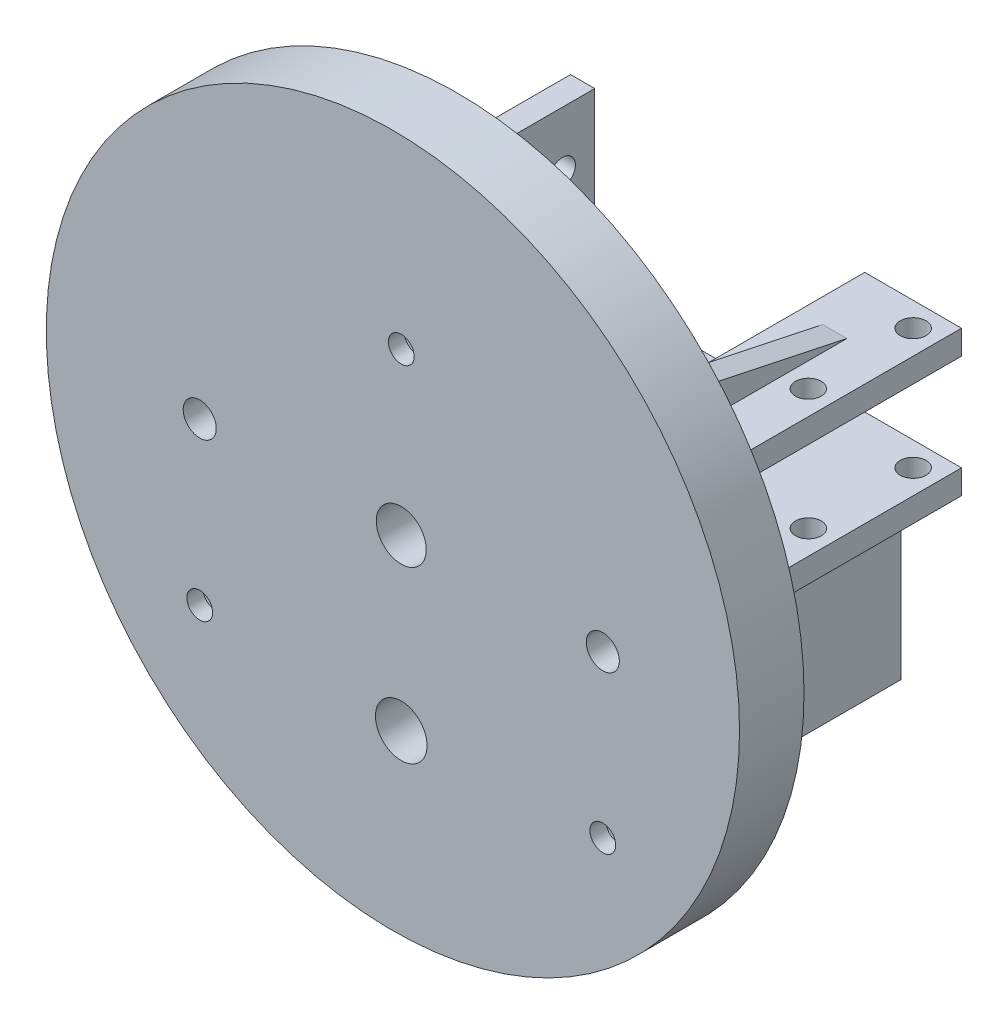
SolidWorks part; units mm, degrees
note: The reader was unsure of these and kept them because the rebuilt part matched: shared geometry of "草图3<3>".
other "标注1"
sketch "草图26" plane through (27.5168, 21.5, -20) normal (0.041, 0.0491, -0.998) x (-0.9988, -0.0263, -0.0424)
ref_plane "前视基准面" through (0, 0, 0) normal (0, 0, 1) x (1, 0, 0)
ref_plane "上视基准面" through (0, 0, 0) normal (0, 1, 0) x (1, 0, 0)
ref_plane "右视基准面" through (0, 0, 0) normal (1, 0, 0) x (0, 0, -1)
sketch "草图1" plane through (0, 0, 0) normal (0, 0, 1) x (1, 0, 0)
  circle A0 centre (-0.5179, 0) radius 21.5
  dimension "D1" = 43
extrude "凸台-拉伸1" add sketch "草图1" along normal blind 4
sketch "草图2" plane through (0, 0, 0) normal (0, 0, -1) x (-1, 0, 0)
  circle A0 centre (0, 0) radius 1.55
  dimension "D1" = 3.1
extrude "切除-拉伸1" cut sketch "草图2" against normal through all
sketch "草图3" plane through (0, 0, 0) normal (0, 0, -1) x (-1, 0, 0)
  line L0 (0, -21.0862) -> (0, 21.0862) construction
  line L1 (-27.5168, 0) -> (27.5168, 0) construction
  line L2 (12.5, 0) -> (12.5, -10) construction
  circle A0 centre (0, 10) radius 2.5
  circle A1 centre (12.5, 0) radius 1.025
  circle A2 centre (12.5, -10) radius 2.5
  circle A3 centre (-12.5, -10) radius 2.5
  circle A4 centre (-12.5, 0) radius 1.025
  point P5 (0, 0)
  point P9 (0, 0)
  dimension "D1" = 5
  dimension "D2" = 2.05
  dimension "D5" = 5
  dimension "D3" = 10
  dimension "D4" = 10
  dimension "D6" = 12.5
extrude "切除-拉伸4" cut sketch "草图3" against normal through all contours A4 | A1 | A0
extrude "切除-拉伸5" cut sketch "草图3<3>" against normal blind 3 contours A2 | A3 | A0
sketch "草图3<3>" plane through (0, 0, 0) normal (0, 0, -1) x (-1, 0, 0) same geometry as "草图3"
sketch "草图4" plane through (0, 0, 0) normal (0, 0, -1) x (-1, 0, 0)
  circle A0 centre (0, 10) radius 0.8
  circle A1 centre (-12.5, -10) radius 0.8
  circle A2 centre (12.5, -10) radius 0.8
  dimension "D1" = 1.6
  dimension "D2" = 1.6
  dimension "D3" = 1.6
extrude "切除-拉伸6" cut sketch "草图4" against normal through all
sketch "草图5" plane through (0, 0, 0) normal (0, 0, -1) x (-1, 0, 0)
  line L0 (0, 0) -> (0, -10.5) construction
  line L1 (0, -21.0862) -> (0, 21.0862) construction
  circle A0 centre (0, -10.5) radius 1.6
  dimension "D2" = 3.2
  dimension "D1" = 10.5
extrude "切除-拉伸7" cut sketch "草图5" against normal through all
chamfer "倒角1" distance 0.5 angle 45 1 edges at (-1.6, -10.5, 0)
sketch "草图6" plane through (0, 0, 0) normal (0, 0, -1) x (-1, 0, 0)
  line L1 (-6.25, -15.5) -> (6.25, -15.5)
  line L2 (-6.25, -15.5) -> (-6.25, -5.5)
  line L3 (-6.25, -5.5) -> (6.25, -5.5)
  line L4 (6.25, -15.5) -> (6.25, -5.5)
  line L5 (-6.25, -15.5) -> (6.25, -5.5) construction
  line L6 (-6.25, -5.5) -> (6.25, -15.5) construction
  line L7 (-7, -4.75) -> (7, -4.75)
  line L8 (-7, -4.75) -> (-7, -16.25)
  line L9 (-7, -16.25) -> (7, -16.25)
  line L10 (7, -4.75) -> (7, -16.25)
  point P0 (0, -10.5)
  dimension "D1" = 12.5
  dimension "D2" = 10
  dimension "D3" = 14
  dimension "D4" = 7
  dimension "D5" = 11.5
  dimension "D6" = 5.75
extrude "凸台-拉伸2" add sketch "草图6" along normal blind 20
sketch "草图8" plane through (0, -16.25, 0) normal (0, -1, 0) x (1, 0, 0)
  line L0 (0, 22.4865) -> (0, -22.4865) construction
  line L2 (-4.7894, -4.8268) -> (4.7894, -4.8268) construction
  line L3 (-4.7894, -3.4865) -> (4.7894, -3.4865)
  line L4 (-4.7894, -6.167) -> (4.7894, -6.167)
  line L5 (-4.7894, -10.8268) -> (4.7894, -10.8268) construction
  line L6 (-4.7894, -9.4865) -> (4.7894, -9.4865)
  line L7 (-4.7894, -12.167) -> (4.7894, -12.167)
  line L8 (-4.7894, -16.8268) -> (4.7894, -16.8268) construction
  line L9 (-4.7894, -15.4865) -> (4.7894, -15.4865)
  line L10 (-4.7894, -18.167) -> (4.7894, -18.167)
  arc A0 (-4.7894, -3.4865) -> (-4.7894, -6.167) centre (-4.7894, -4.8268) ccw
  arc A1 (4.7894, -6.167) -> (4.7894, -3.4865) centre (4.7894, -4.8268) ccw
  arc A2 (-4.7894, -9.4865) -> (-4.7894, -12.167) centre (-4.7894, -10.8268) ccw
  arc A3 (4.7894, -12.167) -> (4.7894, -9.4865) centre (4.7894, -10.8268) ccw
  arc A4 (-4.7894, -15.4865) -> (-4.7894, -18.167) centre (-4.7894, -16.8268) ccw
  arc A5 (4.7894, -18.167) -> (4.7894, -15.4865) centre (4.7894, -16.8268) ccw
  point P3 (0, 0)
  point P6 (0, -4.8268)
  point P15 (0, -10.8268)
  point P22 (0, -16.8268)
  dimension "D1" = 3
extrude "切除-拉伸8" cut sketch "草图8" against normal through all
sketch "草图9" plane through (0, 0, 0) normal (0, 0, -1) x (-1, 0, 0)
  line L0 (9.5, 0) -> (15.5, 0) construction
  line L1 (-27.5168, 0) -> (27.5168, 0) construction
  line L2 (0, 0) -> (-4.75, 0)
  line L3 (14.6547, -2.8784) -> (16.1547, -2.8784)
  line L4 (14.6547, -2.8784) -> (14.6547, 3.1216)
  line L5 (14.6547, 3.1216) -> (16.1547, 3.1216)
  line L6 (16.1547, -2.8784) -> (16.1547, 3.1216)
  line L7 (9.5, -3) -> (8, -3)
  line L8 (9.5, -3) -> (9.5, 10)
  line L9 (9.5, 10) -> (8, 10)
  line L10 (8, -3) -> (8, 10)
  line L11 (0, -21.0862) -> (0, 21.0862) construction
  point P6 (12.5, 0)
  dimension "D1" = 6
  dimension "D2" = 1.5
  dimension "D3" = 6
  dimension "D4" = 3
  dimension "D5" = 1.5
  dimension "D6" = 13
  dimension "D7" = 1.5
  dimension "D8" = 4.75
extrude "凸台-拉伸3" add sketch "草图9" along normal blind 16 contours L10 L7 L8 L9 | L3 L6 L5 L4
sketch "草图10" plane through (-16.1547, 0, 0) normal (-1, 0, 0) x (0, 0, 1)
  line L0 (0, 0) -> (-20.9341, 0) construction
  line L2 (-16, -2.8784) -> (-16, 3.1216) construction
  line L3 (-16, -3) -> (-16, 10) construction
  circle A0 centre (-14, 0) radius 0.8
  circle A1 centre (-14, 6.5) radius 0.8
  dimension "D2" = 1.6
  dimension "D4" = 1.6
  dimension "D1" = 2
  dimension "D3" = 2
  dimension "D5" = 6.5
extrude "切除-拉伸9" cut sketch "草图10" against normal through all
sketch "草图11" plane through (0, 0, 0) normal (0, 0, -1) x (-1, 0, 0)
  line L0 (-27.5168, 0) -> (27.5168, 0) construction
  line L1 (0, 0) -> (-4.75, 0) construction
  line L2 (-4.75, -3) -> (-4.75, 3)
  line L7 (-4.75, 4.5) -> (-10.75, 4.5)
  line L8 (-4.75, -3) -> (-10.75, -3)
  line L9 (-4.75, -3) -> (-4.75, -4.5)
  line L10 (-4.75, -4.5) -> (-10.75, -4.5)
  line L11 (-10.75, -3) -> (-10.75, -4.5)
  line L12 (-10.75, 3) -> (-10.75, 4.5)
  line L13 (-4.75, 3) -> (-10.75, 3)
  line L14 (-4.75, 3) -> (-4.75, 4.5)
  point P7 (-4.75, 0)
  dimension "D1" = 4.75
  dimension "D2" = 6
  dimension "D3" = 6
  dimension "D4" = 1.5
extrude "凸台-拉伸4" add sketch "草图11" along normal blind 20 contours L8 L11 L10 L9 | L13 L14 L7 L12
sketch "草图12" plane through (0, 4.5, 0) normal (0, 1, 0) x (1, 0, 0)
  line L0 (10.75, 20) -> (10.75, 0) construction
  line L1 (4.75, 20) -> (10.75, 20) construction
  circle A0 centre (9.25, 18.5) radius 0.8
  circle A1 centre (9.25, 12) radius 0.8
  dimension "D2" = 1.6
  dimension "D3" = 1.6
  dimension "D1" = 6.5
  dimension "D4" = 1.5
  dimension "D5" = 1.5
extrude "切除-拉伸10" cut sketch "草图12" against normal through all
sketch "草图19" plane through (0, 0, 0) normal (0, 1, 0) x (1, 0, 0)
  line L0 (-16.1547, 10.6608) -> (-19.5716, 0)
  line L1 (-16.1547, 16) -> (-16.1547, 0) construction
  line L2 (27.5168, 0) -> (-27.5168, 0) construction
rib "筋12" sketch "草图19" sketch "草图19" thickness 3 extrusion direction parallel to sketch draft on no parameters "D1"=3
sketch "草图22" plane through (0, 0, 0) normal (0, 1, 0) x (1, 0, 0)
  line L0 (-8, 10.0695) -> (-4.2376, 0)
  line L1 (-8, 16) -> (-8, 0) construction
  line L2 (27.5168, 0) -> (-27.5168, 0) construction
rib "筋14" sketch "草图22" sketch "草图22" thickness 6 parameters "D1"=6
ref_plane "基准面2" through (7, 0, 0) normal (1, 0, 0) x (0, 0, -1)
sketch "草图24" plane through (7, 0, 0) normal (1, 0, 0) x (0, 0, -1)
  line L0 (15.8938, 4.5) -> (0, 7.8721)
  line L1 (20, 4.5) -> (0, 4.5) construction
  line L2 (0, -21.0862) -> (0, 21.0862) construction
rib "筋44" sketch "草图24" sketch "草图24" thickness 1.5 extrusion direction parallel to sketch draft on no parameters "D1"=1.5
sketch "草图25" plane through (7, 0, 0) normal (1, 0, 0) x (0, 0, -1)
  line L0 (19.0824, -4.5) -> (0, -8.3105)
  line L1 (20, -4.5) -> (0, -4.5) construction
  line L2 (0, -12.5) -> (0, -7.5) construction
rib "筋46" sketch "草图25" sketch "草图25" thickness 1 parameters "D1"=1
